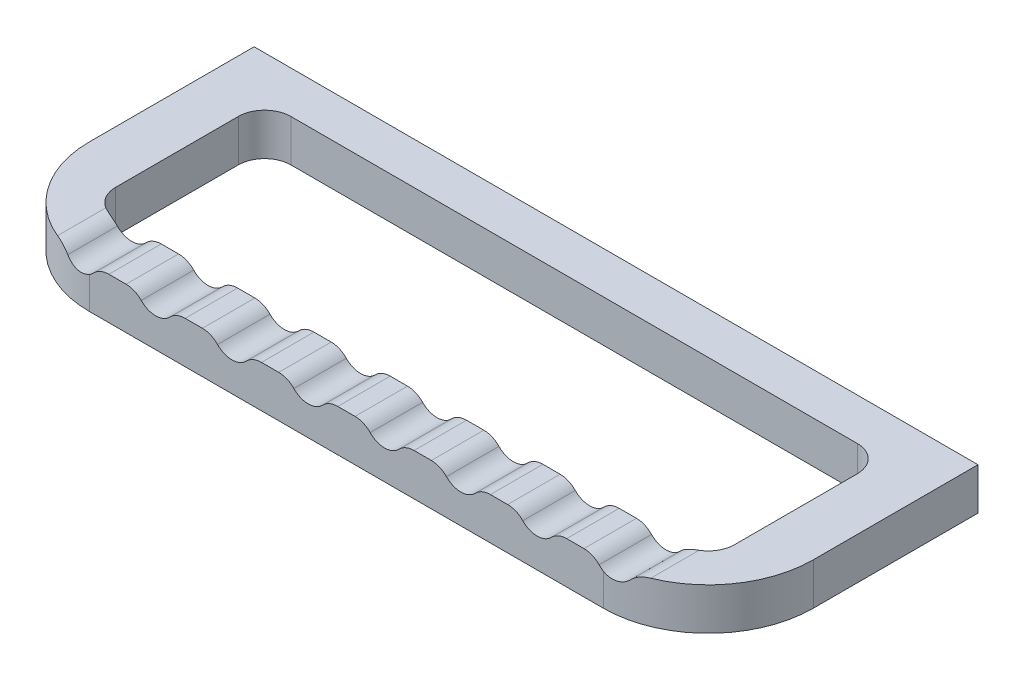
SolidWorks part; units mm, degrees
note: The reader was unsure of these and kept them because the rebuilt part matched: shared geometry of "Sketch1<3>".
ref_plane "Front Plane" through (0, 0, 0) normal (0, 0, 1) x (1, 0, 0)
ref_plane "Top Plane" through (0, 0, 0) normal (0, 1, 0) x (1, 0, 0)
ref_plane "Right Plane" through (0, 0, 0) normal (1, 0, 0) x (0, 0, -1)
sketch "Sketch1" plane through (0, 0, 0) normal (0, 0, 1) x (1, 0, 0)
  line L0 (-43.8099, 2.54) -> (-43.8099, 1.016)
  line L1 (-43.8099, 2.54) -> (43.8099, 2.54)
  line L2 (-43.8099, 2.54) -> (-43.8099, -2.54)
  line L3 (-43.8099, -2.54) -> (43.8099, -2.54)
  line L4 (43.8099, 2.54) -> (43.8099, -2.54)
  line L5 (-43.8099, 2.54) -> (43.8099, -2.54) construction
  line L6 (-43.8099, -2.54) -> (43.8099, 2.54) construction
  line L7 (-43.8099, 1.016) -> (43.8099, 1.016)
  line L8 (43.8099, 1.016) -> (43.8099, 2.54)
  line L9 (0, 0) -> (40.6349, 0)
  line L10 (-43.8099, 2.54) -> (-37.4599, 2.54)
  line L11 (-43.8099, 2.54) -> (-43.8099, -2.54)
  line L12 (-43.8099, -2.54) -> (-37.4599, -2.54)
  line L13 (-37.4599, 2.54) -> (-37.4599, -2.54)
  line L14 (43.8099, -2.54) -> (37.4599, -2.54)
  line L15 (43.8099, -2.54) -> (43.8099, 2.54)
  line L16 (43.8099, 2.54) -> (37.4599, 2.54)
  line L17 (37.4599, -2.54) -> (37.4599, 2.54)
  circle A3 centre (-41.5667, 3.429) radius 2.413
  circle A4 centre (-32.3296, 3.429) radius 2.413
  circle A5 centre (-23.0926, 3.429) radius 2.413
  circle A6 centre (-13.8556, 3.429) radius 2.413
  circle A7 centre (-4.6185, 3.429) radius 2.413
  circle A8 centre (4.6185, 3.429) radius 2.413
  circle A9 centre (13.8556, 3.429) radius 2.413
  circle A10 centre (23.0926, 3.429) radius 2.413
  circle A11 centre (32.3296, 3.429) radius 2.413
  circle A12 centre (41.5667, 3.429) radius 2.413
  point P0 (0, 0)
  dimension "D3" = 1.524
  dimension "D4" = 4.826
  dimension "D1" = 5.08
  dimension "D2" = 87.6198
  dimension "D6" = 6.35
  dimension "D7" = 6.35
  dimension "D8" = 40.6349
  dimension "D5" = 10
extrude "Boss-Extrude1" add sketch "Sketch1" along normal blind 6.35 contours L13 L7 L2 L3 | L3 L17 L7 L13 | L17 L3 L4 L7 | A3 L0 L7 | L1 A3 | A3 L7 L13 L10 | A4 L1 L13 L7 | A5 L1 A4 L7 | A6 L1 A5 L7 | A7 L1 A6 L7 | A8 L1 A7 L7 | A9 L1 A8 L7 | A10 L1 A9 L7 | A11 L1 A10 L7 | A11 L7 L17 L1 | A12 L1 L17 L7 | A12 L7 L4 | L16 A12
fillet "Fillet1" radius 2.54 15 edges at (30.0864, 2.54, 3.175) (34.5729, 2.54, 3.175) (20.8493, 2.54, 3.175) (25.3359, 2.54, 3.175) (11.6123, 2.54, 3.175) (16.0988, 2.54, 3.175) (2.3752, 2.54, 3.175) (6.8618, 2.54, 3.175) (-6.8618, 2.54, 3.175) (-2.3752, 2.54, 3.175) (-16.0988, 2.54, 3.175) (-11.6123, 2.54, 3.175) (-25.3359, 2.54, 3.175) (-20.8493, 2.54, 3.175) (-30.0864, 2.54, 3.175)
extrude "Boss-Extrude2" add sketch "Sketch1<3>" against normal blind 26.289 contours A3 L0 L7 | L1 A3 | A3 L7 L13 L10 | L13 L7 L2 L3 | A12 L7 L4 | L16 A12 | A12 L1 L17 L7 | L17 L3 L4 L7
sketch "Sketch1<3>" plane through (0, 0, 0) normal (0, 0, 1) x (1, 0, 0) same geometry as "Sketch1"
sketch "Sketch2" plane through (0, 0, -26.289) normal (0, 0, -1) x (-1, 0, 0)
  line L0 (37.4599, 2.54) -> (37.4599, -2.54) construction
  line L1 (37.4599, -2.54) -> (43.8099, -2.54) construction
  line L2 (43.8099, -2.54) -> (43.8099, 2.54) construction
  line L3 (43.8099, 2.54) -> (37.4599, 2.54) construction
  line L4 (-43.8099, 2.54) -> (-43.8099, -2.54) construction
  line L5 (-43.8099, -2.54) -> (-37.4599, -2.54) construction
  line L6 (-37.4599, -2.54) -> (-37.4599, 2.54) construction
  line L7 (-37.4599, 2.54) -> (-43.8099, 2.54) construction
  line L8 (37.4599, 2.54) -> (37.4599, -2.54)
  line L9 (37.4599, -2.54) -> (43.8099, -2.54)
  line L10 (43.8099, -2.54) -> (43.8099, 2.54)
  line L11 (43.8099, 2.54) -> (37.4599, 2.54)
  line L12 (-43.8099, 2.54) -> (-43.8099, -2.54)
  line L13 (-43.8099, -2.54) -> (-37.4599, -2.54)
  line L14 (-37.4599, -2.54) -> (-37.4599, 2.54)
  line L15 (-37.4599, 2.54) -> (-43.8099, 2.54)
  line L16 (-43.8099, 2.54) -> (-37.4599, -2.54) construction
  line L17 (-37.4599, 2.54) -> (-43.8099, -2.54) construction
  line L18 (37.4599, 2.54) -> (43.8099, -2.54) construction
  line L19 (43.8099, 2.54) -> (37.4599, -2.54) construction
  circle A0 centre (-40.6349, 0) radius 1.9939
  circle A1 centre (40.6349, 0) radius 1.9939
  dimension "D1" = 3.9878
  dimension "D2" = 3.9878
extrude "Cut-Extrude1" cut sketch "Sketch2" against normal blind 19.05 contours A0 | A1
sketch "Sketch3" plane through (37.4599, 0, 0) normal (-1, 0, 0) x (0, 0, 1)
  line L0 (-26.289, 2.54) -> (0, 2.54) construction
  line L1 (-26.289, -2.54) -> (-21.209, -2.54)
  line L2 (-26.289, -2.54) -> (-26.289, 2.54)
  line L3 (-26.289, 2.54) -> (-21.209, 2.54)
  line L4 (-21.209, -2.54) -> (-21.209, 2.54)
  dimension "D1" = 5.08
extrude "Boss-Extrude3" add sketch "Sketch3" along normal up to surface (74.9198 mm away) up to face at (-37.4599, 0, -13.1445)
fillet "Fillet2" radius 3.175 4 edges at (37.4599, 0, -21.209) (-37.4599, 0, -21.209) (-37.4599, 0, 0) (37.4599, 0, 0)
fillet "Fillet3" radius 12.7 2 edges at (-43.8099, 0, 6.35) (43.8099, 0, 6.35)
